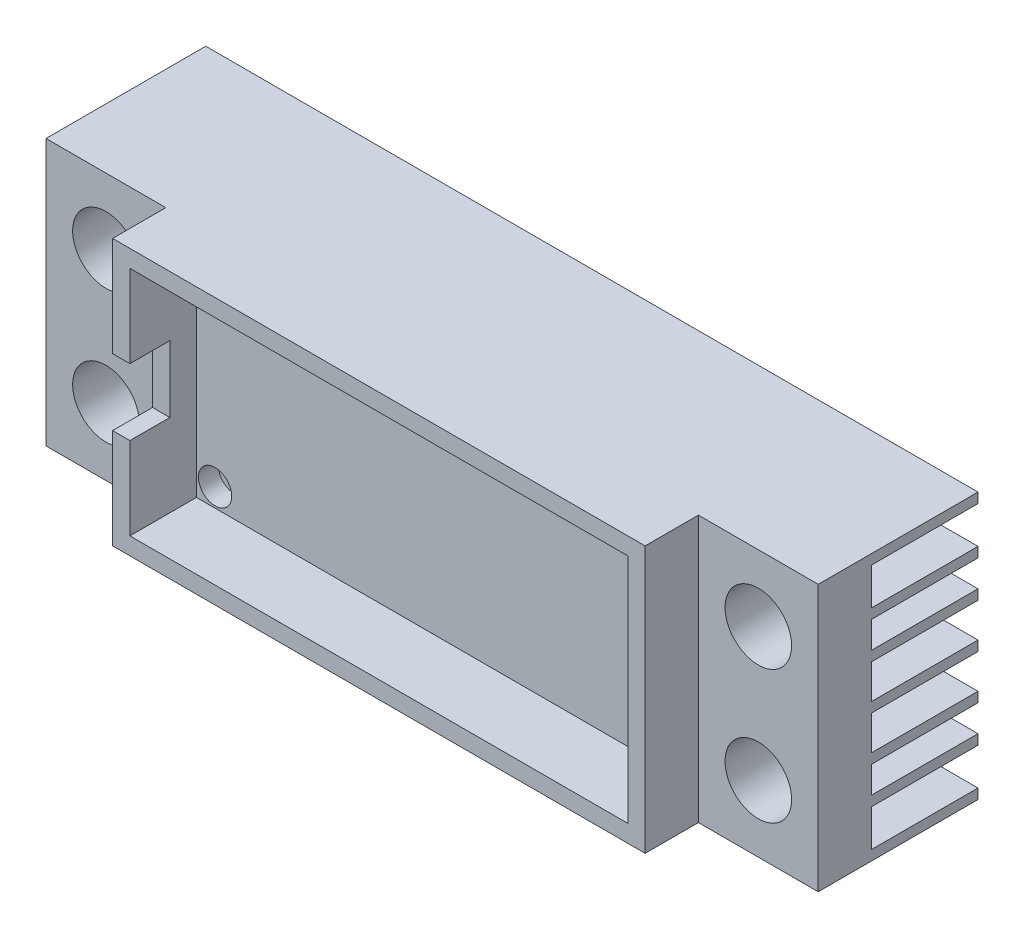
SolidWorks part; units mm, degrees
ref_plane "Front Plane" through (0, 0, 0) normal (0, 0, 1) x (1, 0, 0)
ref_plane "Top Plane" through (0, 0, 0) normal (0, 1, 0) x (1, 0, 0)
ref_plane "Right Plane" through (0, 0, 0) normal (1, 0, 0) x (0, 0, -1)
sketch "Esquisse1" plane through (0, 0, 0) normal (0, 0, 1) x (1, 0, 0)
  line L1 (-40, 20) -> (0, 20)
  line L2 (-40, 20) -> (-40, 0)
  line L3 (-40, 0) -> (0, 0)
  line L4 (0, 20) -> (0, 0)
  dimension "D1" = 40
  dimension "D2" = 20
extrude "Extrusion1" add sketch "Esquisse1" along normal blind 8
sketch "Esquisse2" plane through (0, 0, 8) normal (0, 0, 1) x (1, 0, 0)
  line L0 (-20, 22.9979) -> (-20, -4.2121) construction
  line L1 (-46.4668, 10) -> (2.5983, 10) construction
  line L2 (0, 20) -> (-40, 20) construction
  line L3 (-40, 0) -> (0, 0) construction
  line L4 (-40, 20) -> (-40, 0) construction
  line L5 (0, 0) -> (0, 20) construction
  line L6 (-37.3, 20) -> (-37.3, 17.3) construction
  line L7 (-37.3, 17.3) -> (-40, 17.3) construction
  circle A0 centre (-37.3, 17.3) radius 1.25
  circle A1 centre (-37.3, 2.7) radius 1.25
  circle A2 centre (-2.7, 2.7) radius 1.25
  circle A3 centre (-2.7, 17.3) radius 1.25
  dimension "D1" = 2.5
  dimension "D2" = 2.7
extrude "Extrusion2" cut sketch "Esquisse2" against normal through all
sketch "Esquisse6" plane through (0, 0, 8) normal (0, 0, 1) x (1, 0, 0)
  line L0 (-47.3868, 10) -> (4.3212, 10) construction
  line L1 (-20, 22.3803) -> (-20, -4.0789) construction
  line L2 (0, 0) -> (0, 20) construction
  line L3 (-38.7, 18.7) -> (-1.3, 18.7)
  line L4 (-38.7, 18.7) -> (-38.7, 1.3)
  line L9 (-38.7, 1.3) -> (-1.3, 1.3)
  line L10 (-1.3, 18.7) -> (-1.3, 1.3)
  line L13 (-40, 20) -> (-40, 0) construction
  line L14 (0, 20) -> (-40, 20) construction
  line L15 (-40, 0) -> (0, 0) construction
  line L16 (-38.7, 20) -> (-38.7, 18.7) construction
  line L17 (-40, 18.7) -> (-38.7, 18.7) construction
  line L19 (-40, 20) -> (-40, 0) construction
  line L20 (0, 20) -> (-40, 20) construction
  dimension "D1" = 1.3
extrude "Extrusion9" cut sketch "Esquisse6" against normal blind 5
sketch "Esquisse7" plane through (-40, 0, 0) normal (-1, 0, 0) x (0, 0, 1)
  line L0 (-6.9512, 10) -> (15.4108, 10) construction
  line L3 (5, 12.5) -> (8, 12.5)
  line L5 (5, 12.5) -> (5, 7.5)
  line L7 (8, 12.5) -> (8, 7.5)
  line L8 (5, 7.5) -> (8, 7.5)
  line L10 (8, 0) -> (0, 0) construction
  line L11 (8, 20) -> (0, 20) construction
  line L12 (8, 20) -> (8, 0) construction
  point P15 (8, 10)
  point P16 (5, 10)
  dimension "D1" = 3
  dimension "D2" = 5
sketch "Esquisse8" plane through (0, 0, 0) normal (0, 0, -1) x (-1, 0, 0)
  line L0 (20, 24.9147) -> (20, -5.082) construction
  line L1 (0, 0) -> (0, 20) construction
  line L2 (40, 20) -> (40, 0) construction
  line L3 (-5.3274, 10) -> (47.7683, 10) construction
  line L4 (40, 0) -> (0, 0) construction
  line L5 (0, 20) -> (40, 20) construction
  line L6 (49, 20) -> (40, 20)
  line L7 (49, 20) -> (49, 0)
  line L8 (40, 20) -> (40, 0)
  line L9 (40, 20) -> (40, 0) construction
  line L10 (0, 20) -> (40, 20) construction
  line L11 (49, 0) -> (40, 0)
  line L12 (44.5, 15) -> (40, 15) construction
  line L13 (49, 15) -> (44.5, 15) construction
  line L14 (-9, 0) -> (0, 0)
  line L15 (0, 20) -> (0, 0)
  line L16 (-9, 20) -> (-9, 0)
  line L17 (-9, 20) -> (0, 20)
  circle A1 centre (44.5, 5) radius 2.5
  circle A2 centre (-4.5, 15) radius 2.5
  circle A3 centre (-4.5, 5) radius 2.5
  circle A7 centre (44.5, 15) radius 2.5
  point P23 (40, 10)
  point P24 (49, 10)
  point P31 (0, 10)
  point P32 (-9, 10)
  point P39 (49, 10)
  point P40 (40, 10)
  dimension "D1" = 5
  dimension "D2" = 10
  dimension "D3" = 4.5
extrude "Extrusion11" add sketch "Esquisse8" against normal blind 4
sketch "Esquisse9" plane through (0, 0, 0) normal (0, 0, -1) x (-1, 0, 0)
  circle A0 centre (2.7, 17.3) radius 2.1
  circle A1 centre (37.3, 17.3) radius 2.1
  circle A2 centre (37.3, 2.7) radius 2.1
  circle A3 centre (2.7, 2.7) radius 2.1
  circle A6 centre (2.7, 2.7) radius 1.25 construction
  circle A7 centre (2.7, 17.3) radius 1.25 construction
  circle A8 centre (37.3, 17.3) radius 1.25 construction
  circle A9 centre (37.3, 2.7) radius 1.25 construction
  dimension "D1" = 4.2
extrude "Extrusion12" cut sketch "Esquisse9" against normal blind 1
extrude "Extrusion13" cut sketch "Esquisse7" against normal up to next
sketch "Esquisse10" plane through (0, 0, 0) normal (0, 0, -1) x (-1, 0, 0)
  line L0 (-14.9936, 10) -> (57.3283, 10) construction
  line L2 (-9, 20) -> (49, 20) construction
  line L3 (49, 0) -> (-9, 0) construction
  line L4 (40, 20) -> (40, 12.5) construction
  circle A0 centre (30, 10) radius 4
  dimension "D1" = 8
  dimension "D2" = 10
extrude "Extrusion14" add sketch "Esquisse10" along normal blind 8
sketch "Esquisse12" plane through (0, 0, -8) normal (0, 0, -1) x (-1, 0, 0)
  line L0 (-15.9974, 10) -> (55.1535, 10) construction
  line L1 (-9, 20) -> (49, 20) construction
  line L2 (49, 0) -> (-9, 0) construction
  line L4 (-9, 16.4672) -> (49, 16.4672)
  line L5 (-9, 16.4672) -> (-9, 15.7172)
  line L6 (-9, 15.7172) -> (49, 15.7172)
  line L7 (49, 16.4672) -> (49, 15.7172)
  line L8 (-9, 12.9583) -> (49, 12.9583)
  line L9 (-9, 12.9583) -> (-9, 13.7083)
  line L10 (-9, 13.7083) -> (49, 13.7083)
  line L11 (49, 12.9583) -> (49, 13.7083)
  line L12 (-9, 10.375) -> (49, 10.375)
  line L13 (-9, 10.375) -> (-9, 9.625)
  line L14 (-9, 9.625) -> (49, 9.625)
  line L15 (49, 10.375) -> (49, 9.625)
  line L17 (-9, 20) -> (-9, 0) construction
  line L18 (49, 0) -> (49, 20) construction
  line L19 (-9, 20) -> (49, 20)
  line L20 (-9, 20) -> (-9, 19.25)
  line L21 (-9, 19.25) -> (49, 19.25)
  line L22 (49, 20) -> (49, 19.25)
  line L23 (49, 0) -> (49, 0.75)
  line L24 (-9, 0.75) -> (49, 0.75)
  line L25 (-9, 0) -> (-9, 0.75)
  line L26 (-9, 0) -> (49, 0)
  line L27 (49, 7.0417) -> (49, 6.2917)
  line L28 (-9, 6.2917) -> (49, 6.2917)
  line L29 (-9, 7.0417) -> (-9, 6.2917)
  line L30 (-9, 7.0417) -> (49, 7.0417)
  line L31 (49, 3.5328) -> (49, 4.2828)
  line L32 (-9, 4.2828) -> (49, 4.2828)
  line L33 (-9, 3.5328) -> (-9, 4.2828)
  line L34 (-9, 3.5328) -> (49, 3.5328)
  dimension "D1" = 0.75
extrude "Extrusion15" add sketch "Esquisse12" against normal up to surface (8 mm away) up to face at (2, 15, 0)
sketch "Esquisse13" plane through (0, 0, -8) normal (0, 0, -1) x (-1, 0, 0)
  circle A0 centre (30, 10) radius 4
  circle A1 centre (30, 10) radius 5
  arc A2 (26.0176, 9.625) -> (27.3078, 7.0417) centre (30, 10) ccw construction
  arc A3 (33.9824, 10.375) -> (32.6922, 12.9583) centre (30, 10) ccw construction
  dimension "D1" = 1
extrude "Extrusion16" cut sketch "Esquisse13" against normal up to surface (8 mm away) up to face at (-42.3193, 12.0409, 0)
sketch "Esquisse14" plane through (0, 0, 1) normal (0, 0, -1) x (-1, 0, 0)
  line L2 (0, 20) -> (40, 20)
  line L6 (0, 20) -> (0, 0)
  line L7 (0, 0) -> (40, 0)
  line L8 (40, 20) -> (40, 0)
extrude "Extrusion17" add sketch "Esquisse14" against normal blind 0.5
